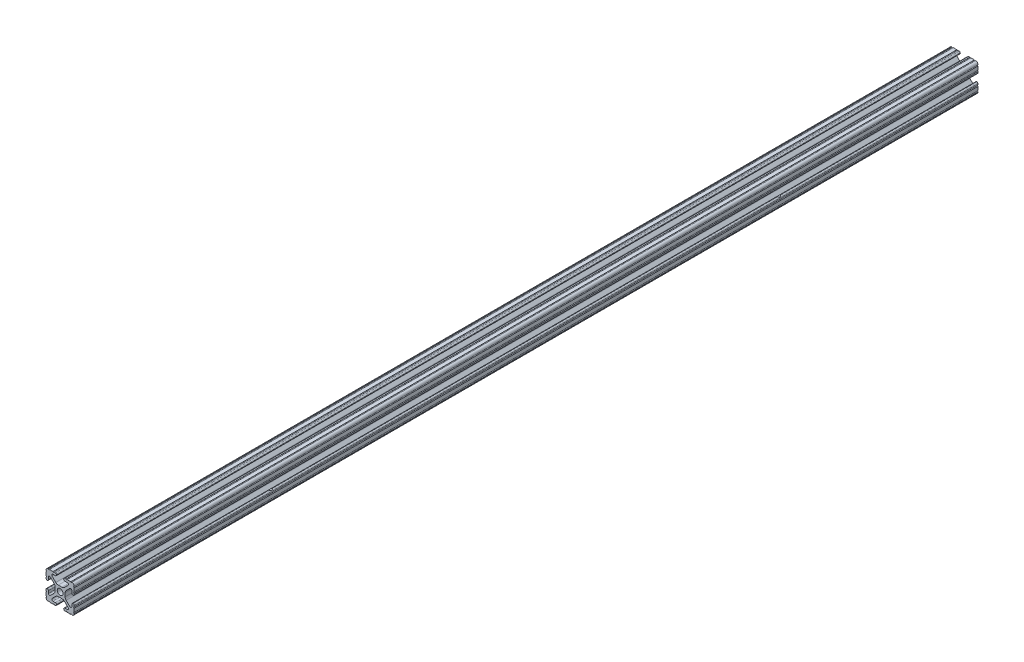
SolidWorks part; units mm, degrees
ref_plane "Front Plane" through (0, 0, 0) normal (0, 0, 1) x (1, 0, 0)
ref_plane "Top Plane" through (0, 0, 0) normal (0, 1, 0) x (1, 0, 0)
ref_plane "Right Plane" through (0, 0, 0) normal (1, 0, 0) x (0, 0, -1)
sketch "Sketch1" plane through (0, 0, 0) normal (0, 0, 1) x (1, 0, 0)
  line L88 (-7.1797, -8.6452) -> (-3.9523, -5.4237)
  line L89 (-1.7093, -4.4958) -> (1.7093, -4.4958)
  line L90 (3.9523, -5.4237) -> (7.1797, -8.6452)
  line L91 (6.4164, -10.4902) -> (4.2875, -10.4902)
  line L92 (3.2385, -11.5392) -> (3.2385, -11.651)
  line L93 (4.2875, -12.7) -> (5.3171, -12.7)
  line L94 (6.3331, -12.7) -> (9.5504, -12.7)
  line L95 (12.7, -9.5504) -> (12.7, -6.3331)
  line L96 (12.7, -5.3171) -> (12.7, -4.2875)
  line L97 (11.651, -3.2385) -> (11.5392, -3.2385)
  line L98 (10.4902, -4.2875) -> (10.4902, -6.4021)
  line L99 (8.7371, -7.1294) -> (5.441, -3.8408)
  line L100 (4.5085, -1.5932) -> (4.5085, 1.5932)
  line L101 (5.441, 3.8408) -> (8.7371, 7.1294)
  line L102 (10.4902, 6.4021) -> (10.4902, 4.2875)
  line L103 (11.5392, 3.2385) -> (11.651, 3.2385)
  line L104 (12.7, 4.2875) -> (12.7, 5.3171)
  line L105 (12.7, 6.3331) -> (12.7, 9.5504)
  line L106 (9.5504, 12.7) -> (6.3331, 12.7)
  line L107 (5.3171, 12.7) -> (4.2875, 12.7)
  line L108 (3.2385, 11.651) -> (3.2385, 11.5392)
  line L109 (4.2875, 10.4902) -> (6.4768, 10.4902)
  line L110 (7.207, 8.7244) -> (3.8983, 5.4232)
  line L111 (1.6558, 4.4958) -> (-1.6558, 4.4958)
  line L112 (-3.8983, 5.4232) -> (-7.207, 8.7244)
  line L113 (-6.4768, 10.4902) -> (-4.2875, 10.4902)
  line L114 (-3.2385, 11.5392) -> (-3.2385, 11.651)
  line L115 (-4.2875, 12.7) -> (-5.3171, 12.7)
  line L116 (-6.3331, 12.7) -> (-9.5504, 12.7)
  line L117 (-12.7, 9.5504) -> (-12.7, 6.3331)
  line L118 (-12.7, 5.3171) -> (-12.7, 4.2875)
  line L119 (-11.651, 3.2385) -> (-11.5392, 3.2385)
  line L120 (-10.4902, 4.2875) -> (-10.4902, 6.4021)
  line L121 (-8.7371, 7.1294) -> (-5.441, 3.8408)
  line L122 (-4.5085, 1.5932) -> (-4.5085, -1.5932)
  line L123 (-5.441, -3.8408) -> (-8.7371, -7.1294)
  line L124 (-10.4902, -6.4021) -> (-10.4902, -4.2875)
  line L125 (-11.5392, -3.2385) -> (-11.651, -3.2385)
  line L126 (-12.7, -4.2875) -> (-12.7, -5.3171)
  line L127 (-12.7, -6.3331) -> (-12.7, -9.5504)
  line L128 (-9.5504, -12.7) -> (-6.3331, -12.7)
  line L129 (-5.3171, -12.7) -> (-4.2875, -12.7)
  line L130 (-3.2385, -11.651) -> (-3.2385, -11.5392)
  line L131 (-4.2875, -10.4902) -> (-6.4164, -10.4902)
  circle A1 centre (0, 0) radius 2.6035
  arc A104 (-7.1797, -8.6452) -> (-6.4164, -10.4902) centre (-6.4164, -9.4098) ccw
  arc A105 (-1.7093, -4.4958) -> (-3.9523, -5.4237) centre (-1.7093, -7.6708) ccw
  arc A106 (3.9523, -5.4237) -> (1.7093, -4.4958) centre (1.7093, -7.6708) ccw
  arc A107 (6.4164, -10.4902) -> (7.1797, -8.6452) centre (6.4164, -9.4098) ccw
  arc A108 (4.2875, -10.4902) -> (3.2385, -11.5392) centre (4.2875, -11.5392) ccw
  arc A109 (3.2385, -11.651) -> (4.2875, -12.7) centre (4.2875, -11.651) ccw
  arc A110 (6.3331, -12.7) -> (5.3171, -12.7) centre (5.8251, -12.7) ccw
  arc A111 (10.5664, -12.6998) -> (9.5504, -12.7) centre (10.0584, -12.7) ccw
  arc A112 (10.5664, -12.6998) -> (12.6998, -10.5664) centre (10.5918, -10.5918) ccw
  arc A113 (12.7, -9.5504) -> (12.6998, -10.5664) centre (12.7, -10.0584) ccw
  arc A114 (12.7, -5.3171) -> (12.7, -6.3331) centre (12.7, -5.8251) ccw
  arc A115 (12.7, -4.2875) -> (11.651, -3.2385) centre (11.651, -4.2875) ccw
  arc A116 (11.5392, -3.2385) -> (10.4902, -4.2875) centre (11.5392, -4.2875) ccw
  arc A117 (8.7371, -7.1294) -> (10.4902, -6.4021) centre (9.4628, -6.4021) ccw
  arc A118 (4.5085, -1.5932) -> (5.441, -3.8408) centre (7.6835, -1.5932) ccw
  arc A119 (5.441, 3.8408) -> (4.5085, 1.5932) centre (7.6835, 1.5932) ccw
  arc A120 (10.4902, 6.4021) -> (8.7371, 7.1294) centre (9.4628, 6.4021) ccw
  arc A121 (10.4902, 4.2875) -> (11.5392, 3.2385) centre (11.5392, 4.2875) ccw
  arc A122 (11.651, 3.2385) -> (12.7, 4.2875) centre (11.651, 4.2875) ccw
  arc A123 (12.7, 6.3331) -> (12.7, 5.3171) centre (12.7, 5.8251) ccw
  arc A124 (12.6998, 10.5664) -> (12.7, 9.5504) centre (12.7, 10.0584) ccw
  arc A125 (12.6998, 10.5664) -> (10.5664, 12.6998) centre (10.5918, 10.5918) ccw
  arc A126 (9.5504, 12.7) -> (10.5664, 12.6998) centre (10.0584, 12.7) ccw
  arc A127 (5.3171, 12.7) -> (6.3331, 12.7) centre (5.8251, 12.7) ccw
  arc A128 (4.2875, 12.7) -> (3.2385, 11.651) centre (4.2875, 11.651) ccw
  arc A129 (3.2385, 11.5392) -> (4.2875, 10.4902) centre (4.2875, 11.5392) ccw
  arc A130 (7.207, 8.7244) -> (6.4768, 10.4902) centre (6.4768, 9.4563) ccw
  arc A131 (1.6558, 4.4958) -> (3.8983, 5.4232) centre (1.6558, 7.6708) ccw
  arc A132 (-3.8983, 5.4232) -> (-1.6558, 4.4958) centre (-1.6558, 7.6708) ccw
  arc A133 (-6.4768, 10.4902) -> (-7.207, 8.7244) centre (-6.4768, 9.4563) ccw
  arc A134 (-4.2875, 10.4902) -> (-3.2385, 11.5392) centre (-4.2875, 11.5392) ccw
  arc A135 (-3.2385, 11.651) -> (-4.2875, 12.7) centre (-4.2875, 11.651) ccw
  arc A136 (-6.3331, 12.7) -> (-5.3171, 12.7) centre (-5.8251, 12.7) ccw
  arc A137 (-10.5664, 12.6998) -> (-9.5504, 12.7) centre (-10.0584, 12.7) ccw
  arc A138 (-10.5664, 12.6998) -> (-12.6998, 10.5664) centre (-10.5918, 10.5918) ccw
  arc A139 (-12.7, 9.5504) -> (-12.6998, 10.5664) centre (-12.7, 10.0584) ccw
  arc A140 (-12.7, 5.3171) -> (-12.7, 6.3331) centre (-12.7, 5.8251) ccw
  arc A141 (-12.7, 4.2875) -> (-11.651, 3.2385) centre (-11.651, 4.2875) ccw
  arc A142 (-11.5392, 3.2385) -> (-10.4902, 4.2875) centre (-11.5392, 4.2875) ccw
  arc A143 (-8.7371, 7.1294) -> (-10.4902, 6.4021) centre (-9.4628, 6.4021) ccw
  arc A144 (-4.5085, 1.5932) -> (-5.441, 3.8408) centre (-7.6835, 1.5932) ccw
  arc A145 (-5.441, -3.8408) -> (-4.5085, -1.5932) centre (-7.6835, -1.5932) ccw
  arc A146 (-10.4902, -6.4021) -> (-8.7371, -7.1294) centre (-9.4628, -6.4021) ccw
  arc A147 (-10.4902, -4.2875) -> (-11.5392, -3.2385) centre (-11.5392, -4.2875) ccw
  arc A148 (-11.651, -3.2385) -> (-12.7, -4.2875) centre (-11.651, -4.2875) ccw
  arc A149 (-12.7, -6.3331) -> (-12.7, -5.3171) centre (-12.7, -5.8251) ccw
  arc A150 (-12.6998, -10.5664) -> (-12.7, -9.5504) centre (-12.7, -10.0584) ccw
  arc A151 (-12.6998, -10.5664) -> (-10.5664, -12.6998) centre (-10.5918, -10.5918) ccw
  arc A152 (-9.5504, -12.7) -> (-10.5664, -12.6998) centre (-10.0584, -12.7) ccw
  arc A153 (-5.3171, -12.7) -> (-6.3331, -12.7) centre (-5.8251, -12.7) ccw
  arc A154 (-4.2875, -12.7) -> (-3.2385, -11.651) centre (-4.2875, -11.651) ccw
  arc A155 (-3.2385, -11.5392) -> (-4.2875, -10.4902) centre (-4.2875, -11.5392) ccw
extrude "Boss-Extrude1" add sketch "Sketch1" along normal mid plane 812.8
sketch "Sketch2" plane through (0, 4.4958, 0) normal (0, 1, 0) x (1, 0, 0)
  circle A0 centre (0.2407, 250) radius 3.175
  circle A1 centre (0, -250) radius 3.175
  dimension "D1" = 6.35
  dimension "D2" = 250
  dimension "D3" = 6.35
  dimension "D4" = 250
extrude "Cut-Extrude1" cut sketch "Sketch2" against normal through all both and the other way through all contours A1 | A0
sketch "Sketch3" plane through (4.5085, 0, 0) normal (1, 0, 0) x (0, 0, -1)
  line L0 (0, 0) -> (0, -131.3157) construction
  line L1 (406.4, -1.5932) -> (406.4, 1.5932) construction
  circle A0 centre (228.53, 0) radius 3.5
  circle A1 centre (-228.53, 0) radius 3.5
  dimension "D1" = 7
  dimension "D2" = 177.87
extrude "Cut-Extrude2" cut sketch "Sketch3" against normal through all both and the other way through all
